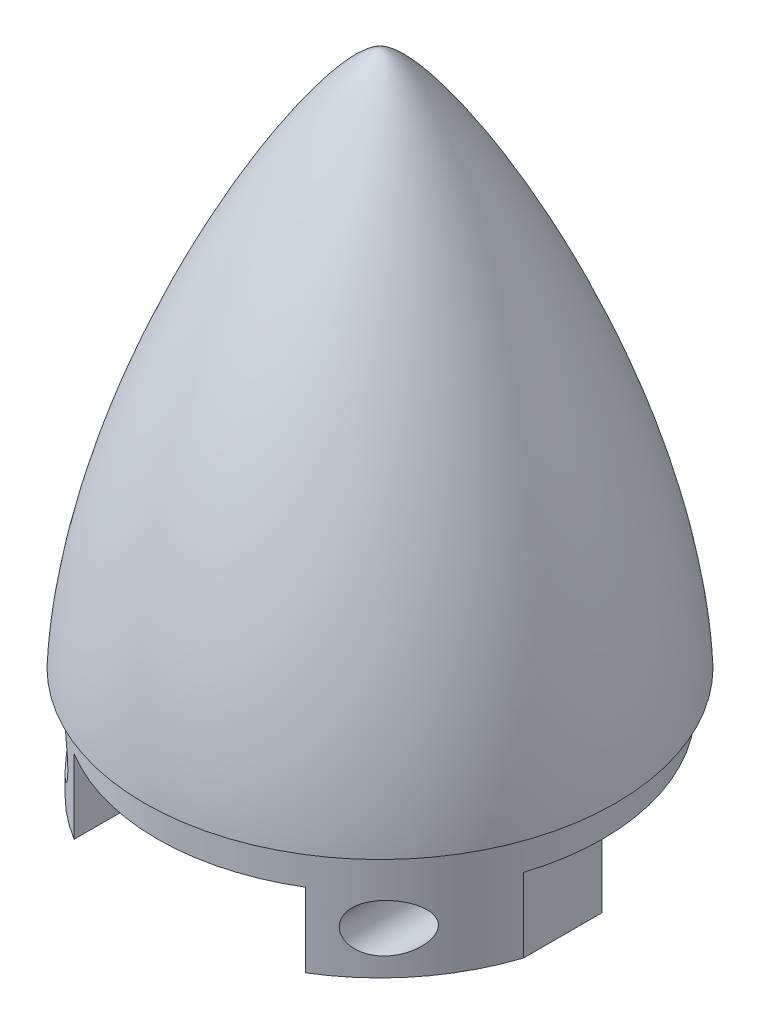
SolidWorks part; units mm, degrees
ref_plane "Front Plane" through (0, 0, 0) normal (0, 0, 1) x (1, 0, 0)
ref_plane "Top Plane" through (0, 0, 0) normal (0, 1, 0) x (1, 0, 0)
ref_plane "Right Plane" through (0, 0, 0) normal (1, 0, 0) x (0, 0, -1)
sketch "Sketch2" plane through (0, 0, 0) normal (0, 0, 1) x (1, 0, 0)
  line L0 (0, 122.2821) -> (0, 181.6557) construction
  line L2 (0, 118.7821) -> (-19.8, 118.7821)
  line L3 (0, 56.9358) -> (0, 97.5144) construction
  line L4 (-20.8, 119.7821) -> (-20.8, 122.2821)
  line L5 (-20.8, 122.2821) -> (-22, 122.2821)
  line L6 (0, 118.7821) -> (0, 172.2821)
  line L7 (-19.8, 118.7821) -> (-20.8, 118.7821)
  line L8 (-22, 122.2821) -> (-20.8412, 144.352) construction
  line L9 (-20.8412, 144.352) -> (-4.2075, 171.8397) construction
  line L10 (-4.2075, 171.8397) -> (0, 172.2821) construction
  line L12 (-20.8, 118.7821) -> (-20.8, 119.7821)
  spline S0 degree 3 poles (-22, 122.2821) (-20.8412, 144.352) (-4.2075, 171.8397) (0, 172.2821) knots 0 0 0 0 1 1 1 1
  point P6 (-20.8, 118.7821)
  dimension "D1" = 3.5
  dimension "D2" = 50
  dimension "D3" = 1.2
  dimension "D4" = 22
revolve "Revolve3" add sketch "Sketch2" angle 360 about L0
sketch "Sketch3" plane through (0, 0, -0.619) normal (0, 0, -1) x (-1, 0, 0)
  line L0 (19.8, 118.7821) -> (19.8, 111.8518)
  line L1 (19.8, 111.8518) -> (10.8, 111.8518)
  line L2 (10.8, 111.8518) -> (10.8, 118.7821)
  line L3 (0, 118.7821) -> (19.8, 118.7821) construction
  line L4 (10.8, 118.7821) -> (19.8, 118.7821)
  circle A0 centre (14.9288, 115.8771) radius 1.15
  dimension "D2" = 2.3
  dimension "D1" = 9
extrude "Boss-Extrude1" add sketch "Sketch3" along normal up to surface (16.8573 mm away) from offset 0.3 up to face at (0, 118.7821, -20.8)
sketch "Sketch4" plane through (0, 0, 0.981) normal (0, 0, 1) x (1, 0, 0)
  line L0 (0, 97.5144) -> (0, 105.7354) construction
  line L1 (-19.8, 118.7821) -> (-10.8, 118.7821)
  line L2 (-19.8, 118.7821) -> (-19.8, 111.8518)
  line L3 (-19.8, 111.8518) -> (-10.8, 111.8518)
  line L4 (-10.8, 118.7821) -> (-10.8, 111.8518)
  line L5 (10.8, 118.7821) -> (10.8, 111.8518)
  line L6 (19.8, 111.8518) -> (10.8, 111.8518)
  line L7 (19.8, 118.7821) -> (19.8, 111.8518)
  line L8 (19.8, 118.7821) -> (10.8, 118.7821)
  circle A0 centre (-14.9288, 115.8771) radius 1.15
  circle A1 centre (14.9288, 115.8771) radius 1.15
extrude "Boss-Extrude2" add sketch "Sketch4" along normal up to surface (16.4954 mm away) from offset 0.3 up to face at (-7.65, 115.317, -6.0371)
ref_plane "Plane1" through (0, 0, -20.8) normal (0, 0, -1) x (-1, 0, 0)
sketch "Sketch5" plane through (0, 0, -20.8) normal (0, 0, -1) x (-1, 0, 0)
  circle A0 centre (14.9288, 115.8771) radius 2.5
  dimension "D1" = 5
extrude "Cut-Extrude1" cut sketch "Sketch5" against normal blind 13
ref_plane "Plane2" through (0, 0, 20.8) normal (0, 0, 1) x (1, 0, 0)
sketch "Sketch6" plane through (0, 0, 20.8) normal (0, 0, 1) x (1, 0, 0)
  circle A0 centre (-14.9288, 115.8771) radius 2.25
  circle A1 centre (14.9288, 115.8771) radius 2.25
  dimension "D1" = 4.5
  dimension "D2" = 4.5
extrude "Cut-Extrude2" cut sketch "Sketch6" against normal blind 15.3
sketch "Sketch7" plane through (0, 0, 1.281) normal (0, 0, -1) x (-1, 0, 0)
  line L0 (-10.8, 111.8518) -> (-19.8, 111.8518) construction
  line L1 (-19.8, 118.7821) -> (-17.5716, 118.7821)
  line L2 (-19.8, 118.7821) -> (-19.8, 111.8518)
  line L3 (-19.8, 111.8518) -> (-17.5716, 111.8518)
  line L4 (-17.5716, 118.7821) -> (-17.5716, 111.8518)
  line L5 (0, 118.7821) -> (0, 111.8518) construction
  line L6 (17.5716, 118.7821) -> (17.5716, 111.8518)
  line L7 (19.8, 111.8518) -> (17.5716, 111.8518)
  line L8 (19.8, 118.7821) -> (19.8, 111.8518)
  line L9 (19.8, 118.7821) -> (17.5716, 118.7821)
extrude "Boss-Extrude3" add sketch "Sketch7" along normal up to surface (2.2 mm away) up to face at (-15.3, 115.317, -0.919)
